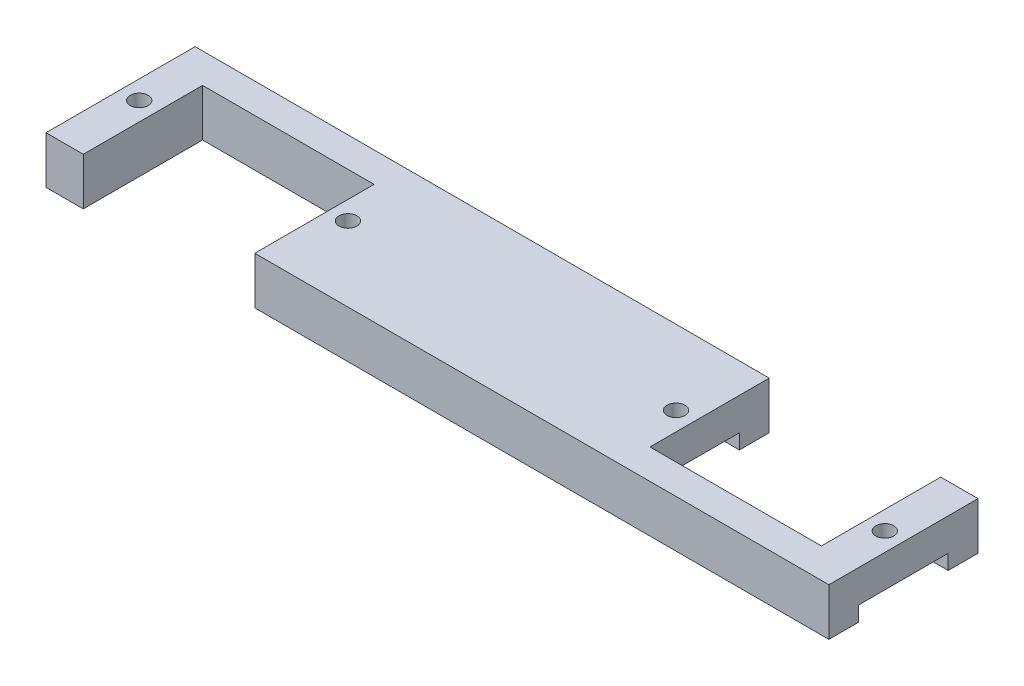
SolidWorks part; units mm, degrees
material "ABS"
ref_plane "Front" through (0, 0, 0) normal (0, 0, 1) x (1, 0, 0)
ref_plane "Top" through (0, 0, 0) normal (0, 1, 0) x (1, 0, 0)
ref_plane "Right" through (0, 0, 0) normal (1, 0, 0) x (0, 0, -1)
sketch "Sketch1" plane through (0, 0, 0) normal (0, 1, 0) x (1, 0, 0)
  line L1 (-52.5, 10) -> (52.5, 10)
  line L2 (-52.5, 10) -> (-52.5, -10)
  line L3 (-52.5, -10) -> (52.5, -10)
  line L4 (52.5, 10) -> (52.5, -10)
  line L5 (-52.5, 10) -> (52.5, -10) construction
  line L6 (-52.5, -10) -> (52.5, 10) construction
  point P0 (0, 0)
  dimension "D1" = 105
  dimension "D2" = 20
extrude "Boss-Extrude1" add sketch "Sketch1" along normal blind 6.35
sketch "Sketch3" plane through (0, 6.35, 0) normal (0, 1, 0) x (1, 0, 0)
  line L0 (-52.5, -10) -> (52.5, -10) construction
  line L1 (-47.5, -10) -> (-24.5, -10)
  line L2 (-47.5, -10) -> (-47.5, 6)
  line L3 (-47.5, 6) -> (-24.5, 6)
  line L4 (-24.5, -10) -> (-24.5, 6)
  line L5 (-52.5, 10) -> (-52.5, -10) construction
  line L6 (52.5, 10) -> (-52.5, 10) construction
  line L7 (52.5, -10) -> (52.5, 10) construction
  line L8 (24.5, 10) -> (47.5, 10)
  line L9 (24.5, 10) -> (24.5, -6)
  line L10 (24.5, -6) -> (47.5, -6)
  line L11 (47.5, 10) -> (47.5, -6)
  dimension "D1" = 23
  dimension "D2" = 5
  dimension "D3" = 4
  dimension "D4" = 5
  dimension "D5" = 4
extrude "Cut-Extrude1" cut sketch "Sketch3" against normal through all
sketch "Sketch4" plane through (0, 0, 0) normal (0, -1, 0) x (1, 0, 0)
  line L0 (24.5, -10) -> (24.5, 6) construction
  line L1 (24.5, 6) -> (19.5, 6)
  line L2 (24.5, 6) -> (24.5, -6)
  line L3 (24.5, -6) -> (19.5, -6)
  line L4 (19.5, 6) -> (19.5, -6)
  line L5 (47.5, 6) -> (47.5, -10) construction
  line L6 (47.5, 6) -> (52.5, 6)
  line L7 (47.5, 6) -> (47.5, -6)
  line L8 (47.5, -6) -> (52.5, -6)
  line L9 (52.5, 6) -> (52.5, -6)
  line L10 (24.5, -10) -> (52.5, 10) construction
  line L11 (24.5, 0) -> (47.5, 0) construction
  point P14 (0, 0)
  point P15 (0, 0)
  point P18 (38.5, 0)
  point P19 (0, 0)
  dimension "D1" = 5
  dimension "D2" = 12
extrude "Cut-Extrude2" cut sketch "Sketch4" against normal blind 2
hole_wizard "M2 Clearance Hole1" positions "Sketch7" profile "Sketch8" hole size "M2" standard "ANSI Metric" end condition through all
sketch "Sketch7" plane through (0, 6.35, 0) normal (0, 1, 0) x (1, 0, 0)
  line L0 (-52.5, 0) -> (52.5, 0) construction
  line L1 (-52.5, 10) -> (-52.5, -10) construction
  line L2 (52.5, -10) -> (52.5, 10) construction
  line L3 (24.5, 10) -> (24.5, -6) construction
  line L4 (47.5, -6) -> (47.5, 10) construction
  line L5 (-47.5, 6) -> (-47.5, -10) construction
  line L6 (-24.5, -10) -> (-24.5, 6) construction
  point P9 (-50, 0)
  point P11 (-22, 0)
  point P13 (22, 0)
  point P15 (50, 0)
  dimension "D1" = 2.5
  dimension "D2" = 2.5
  dimension "D3" = 2.5
  dimension "D4" = 2.5
sketch "Sketch8" plane through (50, 6.35, 0) normal (1, 0, 0) x (0, 0, 1)
  line L0 (0, 0) -> (0, 6.35)
  line L1 (0, 6.35) -> (1.2, 6.35)
  line L2 (1.2, 6.35) -> (1.2, 0)
  line L5 (1.2, 0) -> (0, 0)
  line L11 (0, -6.35) -> (0, 107.95) construction
  dimension "Thru Hole Dia." = 2.4
  dimension "Thru Hole Depth" = 6.35
